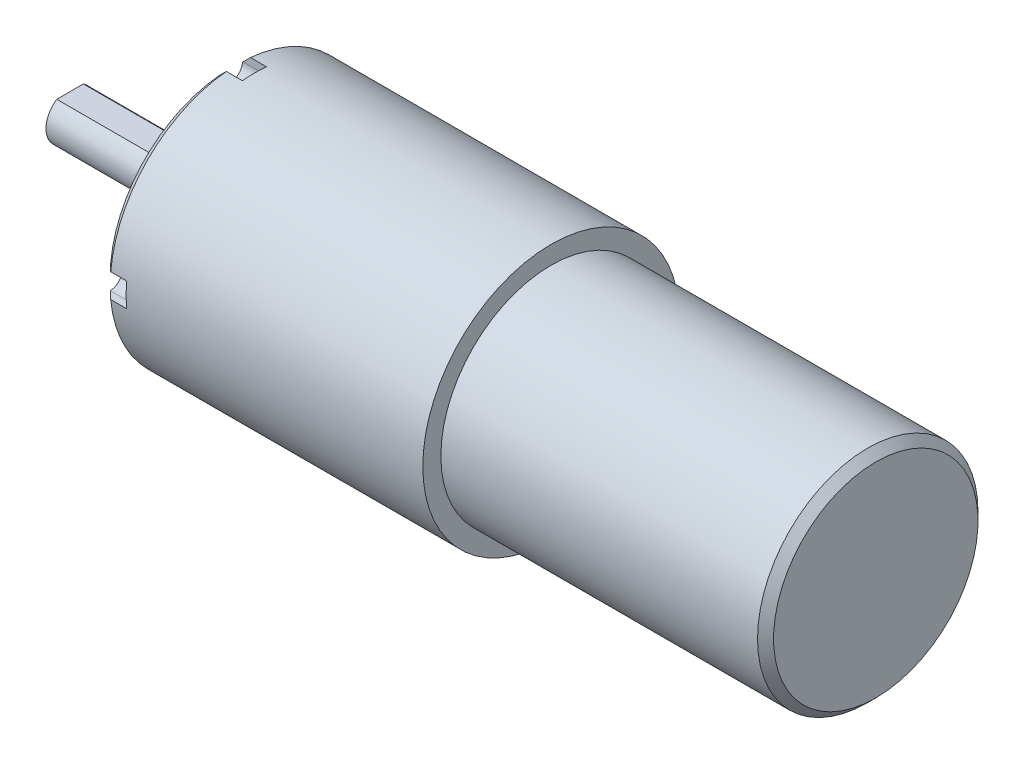
SolidWorks part; units mm, degrees
material "Acier inoxydable moulé"
ref_plane "Plan de face" through (0, 0, 0) normal (0, 0, 1) x (1, 0, 0)
ref_plane "Plan de dessus" through (0, 0, 0) normal (0, 1, 0) x (1, 0, 0)
ref_plane "Plan de droite" through (0, 0, 0) normal (1, 0, 0) x (0, 0, -1)
sketch "Esquisse1" plane through (0, 0, 0) normal (0, 0, 1) x (1, 0, 0)
  line L0 (0, 0) -> (0, 3)
  line L1 (0, 3) -> (17, 3)
  line L2 (17, 3) -> (17, 10)
  line L3 (17, 10) -> (20, 10)
  line L4 (20, 10) -> (20, 16)
  line L5 (20, 16) -> (60, 16)
  line L6 (60, 16) -> (60, 13.75)
  line L7 (60, 13.75) -> (100.5, 13.75)
  line L8 (100.5, 13.75) -> (100.5, 0)
  line L9 (100.5, 0) -> (0, 0)
  dimension "D1" = 3
  dimension "D2" = 17
  dimension "D3" = 3
  dimension "D4" = 40
  dimension "D5" = 40.5
  dimension "D6" = 13.75
  dimension "D7" = 16
  dimension "D8" = 10
revolve "Révolution1" add sketch "Esquisse1" angle 360 about L9
sketch "Esquisse2" plane through (0, 0, 0) normal (-1, 0, 0) x (0, 0, 1)
  line L0 (0, -3) -> (0, 2.5) construction
  line L1 (-1.6583, 2.5) -> (1.6583, 2.5)
  circle A0 centre (0, 0) radius 3 construction
  circle A1 centre (0, 0) radius 3 construction
  arc A2 (-1.6583, 2.5) -> (1.6583, 2.5) centre (0, 0) cw
  point P11 (0, 2.5)
  circle M2 centre (0, 0) radius 3
  dimension "D1" = 5.5
extrude "Enlèv. mat.-Extru.1" cut sketch "Esquisse2" against normal blind 12 contours L1 M2 region at (0, 2.7015, 0)
sketch "Esquisse3" plane through (17, 0, 0) normal (-1, 0, 0) x (0, 0, 1)
  line L0 (0, 0) -> (9, 0) construction
  line L1 (0, 0) -> (0, 11.5438) construction
  line L2 (9, -4.3589) -> (9, 4.3589)
  line L3 (-9, -4.3589) -> (-9, 4.3589)
  circle A0 centre (0, 0) radius 10 construction
  arc A1 (9, 4.3589) -> (9, -4.3589) centre (0, 0) cw
  arc A2 (9, 4.3589) -> (9, -4.3589) centre (18, 0) ccw
  arc A3 (-9, 4.3589) -> (-9, -4.3589) centre (0, 0) ccw
  point P9 (9, 0)
  circle M5 centre (0, 0) radius 10
  dimension "D1" = 9
extrude "Enlèv. mat.-Extru.2" cut sketch "Esquisse3" against normal blind 3 contours L3 M5 | L2 M5 region at (17, 0, 9.4018) region at (17, 0, -9.4018)
chamfer "Chanfrein1" distance 1 angle 45 1 edges at (20, 16, 0)
sketch "Esquisse4" plane through (20, 0, 0) normal (-1, 0, 0) x (0, 0, 1)
  line L0 (0, 0) -> (16, 0) construction
  line L1 (16, 0) -> (16, 1.5) construction
  line L2 (16, 1.5) -> (15, 1.5)
  line L3 (16, -1.5) -> (16, 1.5)
  line L4 (16, -1.5) -> (15, -1.5)
  line L5 (1.5, -16) -> (1.5, -15)
  line L6 (-1.5, -16) -> (1.5, -16)
  line L7 (-1.5, -16) -> (-1.5, -15)
  line L8 (0, 0) -> (0, -16) construction
  line L9 (0, -16) -> (1.5, -16) construction
  line L10 (-16, -1.5) -> (-15, -1.5)
  line L11 (-16, 1.5) -> (-16, -1.5)
  line L12 (-16, 1.5) -> (-15, 1.5)
  line L13 (0, 0) -> (-16, 0) construction
  line L14 (-16, 0) -> (-16, -1.5) construction
  line L15 (-1.5, 16) -> (-1.5, 15)
  line L16 (1.5, 16) -> (-1.5, 16)
  line L17 (1.5, 16) -> (1.5, 15)
  line L18 (0, 0) -> (0, 16) construction
  line L19 (0, 16) -> (-1.5, 16) construction
  arc A0 (15, 1.5) -> (15, -1.5) centre (15, 0) ccw
  arc A1 (1.5, -15) -> (-1.5, -15) centre (0, -15) ccw
  arc A2 (-15, -1.5) -> (-15, 1.5) centre (-15, 0) ccw
  arc A3 (-1.5, 15) -> (1.5, 15) centre (0, 15) ccw
  point P29 (0, 0)
  dimension "D1" = 1.5
  dimension "D2" = 16
  dimension "D3" = 1
  dimension "D4" = 4
extrude "Enlèv. mat.-Extru.3" cut sketch "Esquisse4" against normal blind 3
sketch "Esquisse5" plane through (23, 0, 0) normal (-1, 0, 0) x (0, 0, 1)
  circle A0 centre (0, 15) radius 0.75
  arc A1 (-1.5, 15) -> (1.5, 15) centre (0, 15) ccw construction
  circle A2 centre (15, 0) radius 0.75
  circle A3 centre (0, -15) radius 0.75
  circle A4 centre (-15, 0) radius 0.75
  point P14 (0, 0)
  dimension "D1" = 1.5
  dimension "D2" = 0
  dimension "D3" = 4
extrude "Boss.-Extru.1" add sketch "Esquisse5" along normal blind 0.5
fillet "Congé1" radius 0.5 4 edges at (22.5, -15.75, 0) (22.5, -0.75, -15) (22.5, 14.25, 0) (22.5, -0.75, 15)
sketch "Esquisse6" plane through (20, 0, 0) normal (-1, 0, 0) x (0, 0, 1)
  line L0 (0, 0) -> (26.5964, 0) construction
  line L1 (0, 0) -> (16.5256, 16.5256) construction
  circle A1 centre (9.1924, 9.1924) radius 1.5
  circle A2 centre (9.1924, -9.1924) radius 1.5
  circle A3 centre (-9.1924, -9.1924) radius 1.5
  circle A4 centre (-9.1924, 9.1924) radius 1.5
  point P3 (9.1924, 9.1924)
  point P17 (0, 0)
  dimension "D3" = 3
  dimension "D4" = 4
  dimension "D2" = 45
extrude "Enlèv. mat.-Extru.4" cut sketch "Esquisse6" against normal blind 5.5
chamfer "Chanfrein2" distance 1 angle 45 1 edges at (100.5, 13.75, 0)
